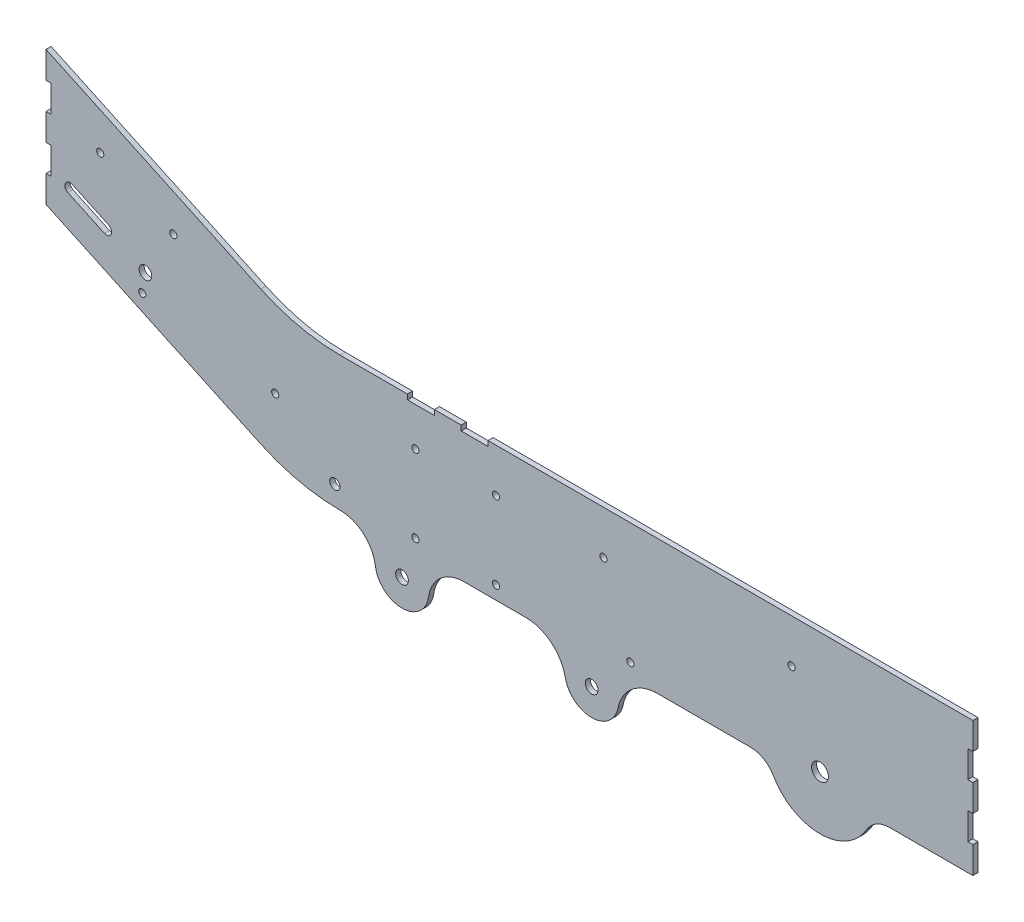
SolidWorks part; units mm, degrees
material "1060 Alloy"
ref_plane "Front Plane" through (0, 0, 0) normal (0, 0, 1) x (1, 0, 0)
ref_plane "Top Plane" through (0, 0, 0) normal (0, 1, 0) x (1, 0, 0)
ref_plane "Right Plane" through (0, 0, 0) normal (1, 0, 0) x (0, 0, -1)
sketch "standoff holes lower" plane through (0, 0, 0) normal (0, 0, 1) x (1, 0, 0)
  circle A7 centre (95.25, 85.725) radius 3.3782
  circle A8 centre (95.25, 12.7) radius 3.3782
  circle A9 centre (171.45, 12.7) radius 3.3782
  circle A10 centre (171.45, 85.725) radius 3.3782
  circle A12 centre (298.45, 12.7) radius 3.3782
  circle A13 centre (450.85, 85.725) radius 3.3782
  circle A16 centre (273.05, 85.725) radius 3.3782
  point P21 (0, 0)
sketch "axle holes lower" plane through (0, 0, 0) normal (0, 0, 1) x (1, 0, 0)
  line L10 (514.35, 98.425) -> (75.4368, 98.425) construction
  line L11 (66.0749, 94.3067) -> (3.3381, 25.8666) construction
  line L12 (0, 17.2849) -> (0, 12.7) construction
  line L13 (12.7, 0) -> (514.35, 0) construction
  line L14 (527.05, 12.7) -> (527.05, 85.725) construction
  circle A1 centre (247.65, 15.24) radius 4.826
  circle A4 centre (19.05, 19.05) radius 4.826
  arc A10 (527.05, 85.725) -> (514.35, 98.425) centre (514.35, 85.725) ccw construction
  arc A11 (75.4368, 98.425) -> (66.0749, 94.3067) centre (75.4368, 85.725) ccw construction
  arc A12 (3.3381, 25.8666) -> (0, 17.2849) centre (12.7, 17.2849) ccw construction
  arc A13 (0, 12.7) -> (12.7, 0) centre (12.7, 12.7) ccw construction
  arc A14 (514.35, 0) -> (527.05, 12.7) centre (514.35, 12.7) ccw construction
  circle A15 centre (476.25, 19.05) radius 4.826
sketch "lower box" plane through (0, 0, 0) normal (0, 0, 1) x (1, 0, 0)
  line L1 (622.3, 0) -> (-254, 0) construction
  line L2 (622.3, 0) -> (622.3, 25.4) construction
  line L3 (622.3, 127) -> (-254, 127) construction
  line L4 (-254, 0) -> (-254, 127) construction
  line L6 (527.05, 12.7) -> (527.05, 85.725) construction
  line L7 (622.3, 101.6) -> (622.3, 127) construction
  line L8 (622.3, 101.6) -> (617.474, 101.6) construction
  line L10 (622.3, 76.2) -> (617.474, 76.2) construction
  line L11 (617.474, 101.6) -> (617.474, 76.2) construction
  line L12 (622.3, 50.8) -> (617.474, 50.8) construction
  line L14 (622.3, 25.4) -> (617.474, 25.4) construction
  line L15 (617.474, 50.8) -> (617.474, 25.4) construction
  line L16 (622.3, 50.8) -> (622.3, 76.2) construction
  dimension "D1" = 127
  dimension "D2" = 876.3
  dimension "D3" = 95.25
  dimension "D4" = 4.826
sketch "alxe holes upper" plane through (0, 0, 0) normal (0, 0, 1) x (1, 0, 0)
  line L0 (-219.7848, 130.4205) -> (-230.5193, 107.4003) construction
  line L1 (-230.5193, 107.4003) -> (8.3155, -3.9702) construction
  line L3 (8.3155, -3.9702) -> (19.05, 19.05) construction
  line L4 (622.3, 0) -> (-254, 0) construction
  circle A0 centre (19.05, 19.05) radius 4.826 construction
  circle A2 centre (-219.7848, 130.4205) radius 4.826
  circle A3 centre (19.05, 19.05) radius 4.826
  dimension "D4" = 25
  dimension "D1" = 25.4
  dimension "D2" = 25.4
  dimension "D3" = 263.525
sketch "standoff holes upper" plane through (0, 0, 0) normal (0, 0, 1) x (1, 0, 0)
  line L0 (-162.9561, 84.3028) -> (-166.1764, 77.3967) construction
  line L1 (-226.6865, 105.613) -> (11.2395, -5.3337) construction
  line L4 (-37.2808, 64.9356) -> (-55.5295, 25.8012) construction
  line L5 (-230.5193, 107.4003) -> (8.3155, -3.9702) construction
  circle A2 centre (-162.9561, 84.3028) radius 3.3782
  circle A3 centre (-37.2808, 64.9356) radius 3.3782
  dimension "D2" = 7.62
  dimension "D1" = 43.18
sketch "upper shadow" plane through (0, 0, 0) normal (0, 0, 1) x (1, 0, 0)
  line L0 (-230.5193, 107.4003) -> (8.3155, -3.9702) construction
  line L4 (33.2535, 40.1076) -> (-204.2179, 150.8423) construction
  line L5 (-230.5193, 107.4003) -> (8.3155, -3.9702) construction
  arc A4 (8.3155, -3.9702) -> (33.2535, 40.1076) centre (19.05, 19.05) ccw construction
  arc A5 (-204.2179, 150.8423) -> (-230.5193, 107.4003) centre (-216.8161, 128.7868) ccw construction
  dimension "D1" = 25.4
  dimension "D2" = 25.4
sketch "upper box" plane through (0, 0, 0) normal (0, 0, 1) x (1, 0, 0)
  line L0 (-15.224, 0) -> (-254, 111.3431) construction
  line L1 (622.3, 0) -> (-254, 0) construction
  line L2 (-254, 111.3431) -> (-254, 136.7431) construction
  line L3 (-254, 238.3431) -> (257.1283, 0) construction
  line L4 (12.7, 0) -> (514.35, 0) construction
  line L5 (-254, 0) -> (-254, 127) construction
  line L6 (-230.5193, 107.4003) -> (8.3155, -3.9702) construction
  line L7 (-254, 212.9431) -> (-254, 238.3431) construction
  line L8 (-254, 212.9431) -> (-249.174, 212.9431) construction
  line L9 (-254, 162.1431) -> (-254, 187.5431) construction
  line L10 (-254, 187.5431) -> (-249.174, 187.5431) construction
  line L11 (-249.174, 212.9431) -> (-249.174, 187.5431) construction
  line L12 (-254, 162.1431) -> (-249.174, 162.1431) construction
  line L14 (-254, 136.7431) -> (-249.174, 136.7431) construction
  line L15 (-249.174, 162.1431) -> (-249.174, 136.7431) construction
  dimension "D1" = 127
  dimension "D2" = 6.35
  dimension "D3" = 4.826
sketch "outer face" plane through (0, 0, 0) normal (0, 0, 1) x (1, 0, 0)
  line L0 (622.3, 0) -> (-254, 0) construction
  line L1 (622.3, 0) -> (622.3, 25.4) construction
  line L2 (622.3, 25.4) -> (617.474, 25.4) construction
  line L3 (617.474, 50.8) -> (617.474, 25.4) construction
  line L4 (622.3, 50.8) -> (617.474, 50.8) construction
  line L5 (622.3, 50.8) -> (622.3, 76.2) construction
  line L6 (622.3, 76.2) -> (617.474, 76.2) construction
  line L7 (617.474, 101.6) -> (617.474, 76.2) construction
  line L8 (622.3, 101.6) -> (622.3, 127) construction
  line L9 (622.3, 101.6) -> (617.474, 101.6) construction
  line L10 (622.3, 127) -> (-254, 127) construction
  line L11 (-254, 238.3431) -> (257.1283, 0) construction
  line L12 (-254, 212.9431) -> (-254, 238.3431) construction
  line L13 (-254, 212.9431) -> (-249.174, 212.9431) construction
  line L14 (-249.174, 212.9431) -> (-249.174, 187.5431) construction
  line L15 (-249.174, 162.1431) -> (-249.174, 136.7431) construction
  line L16 (-254, 136.7431) -> (-249.174, 136.7431) construction
  line L17 (-254, 111.3431) -> (-254, 136.7431) construction
  line L18 (-15.224, 0) -> (-254, 111.3431) construction
  line L19 (-254, 162.1431) -> (-249.174, 162.1431) construction
  line L20 (-254, 162.1431) -> (-254, 187.5431) construction
  line L21 (-254, 187.5431) -> (-249.174, 187.5431) construction
  line L22 (622.3, 0) -> (24.1933, 0)
  line L23 (622.3, 0) -> (622.3, 25.4)
  line L24 (622.3, 25.4) -> (617.474, 25.4)
  line L25 (617.474, 50.8) -> (617.474, 25.4)
  line L26 (622.3, 50.8) -> (617.474, 50.8)
  line L27 (622.3, 50.8) -> (622.3, 76.2)
  line L28 (622.3, 76.2) -> (617.474, 76.2)
  line L29 (617.474, 101.6) -> (617.474, 76.2)
  line L30 (622.3, 101.6) -> (622.3, 127)
  line L31 (622.3, 101.6) -> (617.474, 101.6)
  line L32 (622.3, 127) -> (24.1933, 127)
  line L33 (-254, 238.3431) -> (-50.9483, 143.6585)
  line L34 (-254, 212.9431) -> (-254, 238.3431)
  line L35 (-254, 212.9431) -> (-249.174, 212.9431)
  line L36 (-249.174, 212.9431) -> (-249.174, 187.5431)
  line L37 (-249.174, 162.1431) -> (-249.174, 136.7431)
  line L38 (-254, 136.7431) -> (-249.174, 136.7431)
  line L39 (-254, 111.3431) -> (-254, 136.7431)
  line L40 (-50.9483, 16.6585) -> (-254, 111.3431)
  line L41 (-254, 162.1431) -> (-249.174, 162.1431)
  line L42 (-254, 162.1431) -> (-254, 187.5431)
  line L43 (-254, 187.5431) -> (-249.174, 187.5431)
  arc A0 (-50.9483, 16.6585) -> (24.1933, 0) centre (24.1933, 177.8) ccw
  arc A1 (24.1933, 127) -> (-50.9483, 143.6585) centre (24.1933, 304.8) cw
  dimension "D1" = 177.8
extrude "Boss-Extrude1" add sketch "outer face" along normal blind 4.826
sketch "Sketch5" plane through (0, 0, 4.826) normal (0, 0, 1) x (1, 0, 0)
  line L0 (-254, 238.3431) -> (257.1283, 0) construction
  line L1 (-162.9561, 84.3028) -> (-120.2162, 175.9587) construction
  line L3 (-202.695, 179.3869) -> (-133.6344, 147.1834) construction
  circle A0 centre (-162.9561, 84.3028) radius 3.3782 construction
  circle A1 centre (-37.2808, 64.9356) radius 3.3782 construction
  circle A2 centre (95.25, 85.725) radius 3.3782 construction
  circle A3 centre (95.25, 12.7) radius 3.3782 construction
  circle A4 centre (171.45, 12.7) radius 3.3782 construction
  circle A5 centre (171.45, 85.725) radius 3.3782 construction
  circle A6 centre (273.05, 85.725) radius 3.3782 construction
  circle A7 centre (298.45, 12.7) radius 3.3782 construction
  circle A8 centre (450.85, 85.725) radius 3.3782 construction
  circle A9 centre (-162.9561, 84.3028) radius 3.3782
  circle A10 centre (-37.2808, 64.9356) radius 3.3782
  circle A11 centre (95.25, 85.725) radius 3.3782
  circle A12 centre (95.25, 12.7) radius 3.3782
  circle A13 centre (171.45, 12.7) radius 3.3782
  circle A14 centre (171.45, 85.725) radius 3.3782
  circle A15 centre (273.05, 85.725) radius 3.3782
  circle A16 centre (298.45, 12.7) radius 3.3782
  circle A17 centre (450.85, 85.725) radius 3.3782
  circle A18 centre (-133.6344, 147.1834) radius 3.3782
  circle A19 centre (-202.695, 179.3869) radius 3.3782
  dimension "D1" = 31.75
  dimension "D2" = 76.2
extrude "standoff hole" cut sketch "Sketch5" against normal through all
sketch "Sketch6" plane through (0, 0, 4.826) normal (0, 0, 1) x (1, 0, 0)
  circle A0 centre (-219.7848, 130.4205) radius 4.826 construction
  circle A1 centre (19.05, 19.05) radius 4.826 construction
  circle A2 centre (247.65, 15.24) radius 4.826 construction
  circle A4 centre (-219.7848, 130.4205) radius 4.826
  circle A5 centre (19.05, 19.05) radius 4.826
  circle A6 centre (247.65, 15.24) radius 4.826 construction
extrude "axle holes" cut sketch "Sketch6" against normal through all
sketch "Sketch7" plane through (0, 0, 4.826) normal (0, 0, 1) x (1, 0, 0)
  line L0 (-231.2949, 135.7877) -> (-196.7645, 119.686) construction
  line L1 (-229.2553, 140.1616) -> (-194.725, 124.0598)
  line L2 (-233.3344, 131.4139) -> (-198.8041, 115.3121)
  line L3 (-230.5193, 107.4003) -> (8.3155, -3.9702) construction
  circle A0 centre (-219.7848, 130.4205) radius 4.826 construction
  circle A1 centre (-219.7848, 130.4205) radius 4.826
  arc A2 (-229.2553, 140.1616) -> (-233.3344, 131.4139) centre (-231.2949, 135.7877) ccw
  arc A3 (-198.8041, 115.3121) -> (-194.725, 124.0598) centre (-196.7645, 119.686) ccw
  point P5 (-214.0297, 127.7369)
  circle M6 centre (-219.7848, 130.4205) radius 4.826
  dimension "D1" = 38.1
  dimension "D2" = 12.7
extrude "front slot" cut sketch "Sketch7" against normal through all contours L1 A2 L2 A1 M6 | L2 A3 L1 region at (-228.975, 134.706, 4.826) region at (-204.8394, 123.4514, 4.826)
sketch "Sketch8" plane through (0, 0, 4.826) normal (0, 0, 1) x (1, 0, 0)
  line L0 (113.0933, 127) -> (113.0933, 122.174) construction
  line L1 (87.6933, 122.174) -> (113.0933, 122.174)
  line L2 (87.6933, 122.174) -> (87.6933, 127)
  line L3 (87.6933, 127) -> (113.0933, 127)
  line L4 (113.0933, 122.174) -> (113.0933, 127)
  line L5 (622.3, 127) -> (24.1933, 127) construction
  line L6 (113.0933, 122.174) -> (138.4933, 122.174) construction
  line L7 (138.4933, 122.174) -> (163.8933, 122.174)
  line L8 (138.4933, 122.174) -> (138.4933, 127)
  line L9 (138.4933, 127) -> (163.8933, 127)
  line L10 (163.8933, 122.174) -> (163.8933, 127)
  line L11 (62.2933, 122.174) -> (189.2933, 122.174)
  line L12 (62.2933, 122.174) -> (62.2933, 127)
  line L13 (62.2933, 127) -> (189.2933, 127)
  line L14 (189.2933, 122.174) -> (189.2933, 127)
  line L15 (163.8933, 127) -> (163.8933, 122.174) construction
  point P18 (125.7933, 122.174)
  point P19 (125.7933, 122.174)
  line M29 (622.3, 127) -> (24.1933, 127)
  dimension "D1" = 127
extrude "top slots" cut sketch "Sketch8" against normal through all contours L1 L4 L2 M29 | L7 L10 L8 M29 region at (100.3933, 124.587, 4.826) region at (151.1933, 124.587, 4.826)
sketch "Sketch9" plane through (0, 0, 4.826) normal (0, 0, 1) x (1, 0, 0)
  line L0 (365.4629, -63.5) -> (553.974, -63.5) construction
  line L1 (24.1933, 0) -> (622.3, 0) construction
  line L3 (553.974, -63.5) -> (553.974, 63.787) construction
  line L4 (617.474, 25.4) -> (617.474, 50.8) construction
  line L5 (24.1933, 0) -> (622.3, 0)
  circle A0 centre (477.774, 12.7) radius 76.2 construction
  circle A1 centre (477.774, 12.7) radius 8
  arc A2 (433.7799, -12.7) -> (521.7681, -12.7) centre (477.774, 12.7) ccw
  arc A3 (543.7651, 0) -> (521.7681, -12.7) centre (543.7651, -25.4) ccw
  arc A4 (433.7799, -12.7) -> (411.7829, 0) centre (411.7829, -25.4) ccw
  dimension "D1" = 152.4
  dimension "D4" = 16
  dimension "D5" = 50.8
  dimension "D6" = 25.4
  dimension "D7" = 25.4
  dimension "D2" = 63.5
  dimension "D3" = 63.5
extrude "back axle extension" add sketch "Sketch9" against normal up to surface (4.826 mm away) contours A4 A2 A3 L5 region at (477.774, -15.4671, 4.826) up to face at (-214.0297, 127.7369, 0)
sketch "Sketch11" plane through (0, 0, 4.826) normal (0, 0, 1) x (1, 0, 0)
  line L0 (24.1933, 0) -> (411.7829, 0) construction
  line L1 (24.1933, 0) -> (411.7829, 0)
  line L2 (561.7812, -62.775) -> (321.8375, -62.775) construction
  line L3 (199.6366, 0) -> (324.1114, 0)
  arc A0 (471.7538, 87.9345) -> (489.1691, 87.3098) centre (477.774, 12.7) ccw construction
  arc A1 (471.7538, 87.9345) -> (489.1691, 87.3098) centre (477.774, 12.7) ccw
  circle A2 centre (261.874, -25.5) radius 37.275 construction
  arc A5 (258.0857, 11.582) -> (275.1308, 9.338) centre (261.874, -25.5) ccw construction
  arc A6 (258.0857, 11.582) -> (275.1308, 9.338) centre (261.874, -25.5) ccw construction
  arc A7 (236.9791, -30.54) -> (286.7689, -30.54) centre (261.874, -25.5) ccw
  arc A8 (324.1114, 0) -> (286.7689, -30.54) centre (324.1114, -38.1) ccw
  arc A9 (236.9791, -30.54) -> (199.6366, 0) centre (199.6366, -38.1) ccw
  dimension "D1" = 215.9
  dimension "D2" = 25.4
  dimension "D3" = 38.1
extrude "lower small axle extension" add sketch "Sketch11" against normal up to surface (4.826 mm away) contours A9 A7 A8 L1 region at (261.874, -20.0987, 4.826) up to face at (-214.0297, 127.7369, 0)
sketch "Sketch13" plane through (0, 0, 4.826) normal (0, 0, 1) x (1, 0, 0)
  line L0 (247.3066, -62.775) -> (540.2367, -62.775) construction
  line L1 (-361.4832, 140.4439) -> (-108.3874, 22.4235) construction
  line L2 (-229.2553, 140.1616) -> (-194.725, 124.0598) construction
  line L3 (24.1933, 0) -> (199.6366, 0) construction
  line L4 (24.1933, 0) -> (199.6366, 0)
  arc A0 (471.7538, 87.9345) -> (489.1691, 87.3098) centre (477.774, 12.7) ccw construction
  arc A1 (258.0857, 11.582) -> (275.1308, 9.338) centre (261.874, -25.5) ccw construction
  arc A2 (471.7538, 87.9345) -> (489.1691, 87.3098) centre (477.774, 12.7) ccw construction
  arc A3 (258.0857, 11.582) -> (275.1308, 9.338) centre (261.874, -25.5) ccw construction
  circle A5 centre (82.5849, -25.5) radius 37.275 construction
  arc A6 (-198.8041, 115.3121) -> (-194.725, 124.0598) centre (-196.7645, 119.686) ccw construction
  arc A7 (-198.8041, 115.3121) -> (-194.725, 124.0598) centre (-196.7645, 119.686) ccw construction
  circle A8 centre (-196.7645, 119.686) radius 50.8 construction
  arc A9 (57.4225, -28.9659) -> (107.7473, -28.9659) centre (82.5849, -25.5) ccw
  arc A12 (236.9791, -30.54) -> (286.7689, -30.54) centre (261.874, -25.5) ccw construction
  arc A13 (140.9765, 0) -> (107.7473, -28.9659) centre (140.9765, -33.543) ccw
  arc A14 (57.4225, -28.9659) -> (24.1933, 0) centre (24.1933, -33.543) ccw
  dimension "D1" = 101.6
extrude "front small axle extension" add sketch "Sketch13" against normal up to surface (4.826 mm away) contours A14 A9 A13 L4 region at (82.5849, -20.4486, 4.826) up to face at (-214.0297, 127.7369, 0)
sketch "Sketch14" plane through (0, 0, 4.826) normal (0, 0, 1) x (1, 0, 0)
  line L0 (-254, 111.3431) -> (-50.9483, 16.6585) construction
  line L1 (-254, 111.3431) -> (-50.9483, 16.6585)
  line L2 (-267.5177, 96.6271) -> (94.0166, -71.9591) construction
  line L3 (-227.5206, 77.9761) -> (-175.6892, 189.1288) construction
  arc A0 (78.7966, 11.582) -> (95.8417, 9.338) centre (82.5849, -25.5) ccw construction
  arc A1 (78.7966, 11.582) -> (95.8417, 9.338) centre (82.5849, -25.5) ccw
  circle A2 centre (-160.0111, 102.5476) radius 50.8 construction
  dimension "D1" = 101.6
  dimension "D2" = 38.1
sketch "Sketch10" plane through (0, 0, 4.826) normal (0, 0, 1) x (1, 0, 0)
  circle A0 centre (477.774, 12.7) radius 8
  circle A1 centre (261.874, -25.5) radius 6
  circle A2 centre (82.5849, -25.5) radius 6
  circle A3 centre (-160.0111, 102.5476) radius 6
  dimension "D1" = 16
  dimension "D2" = 12
  dimension "D3" = 12
extrude "new axle holes" cut sketch "Sketch10" against normal through all
equation "\"w\"= .19"
equation "\"D4@lower box\" = \"w\""
equation "\"D3@upper box\"=\"w\""
equation "\"D1@Boss-Extrude1\"=\"w\""
